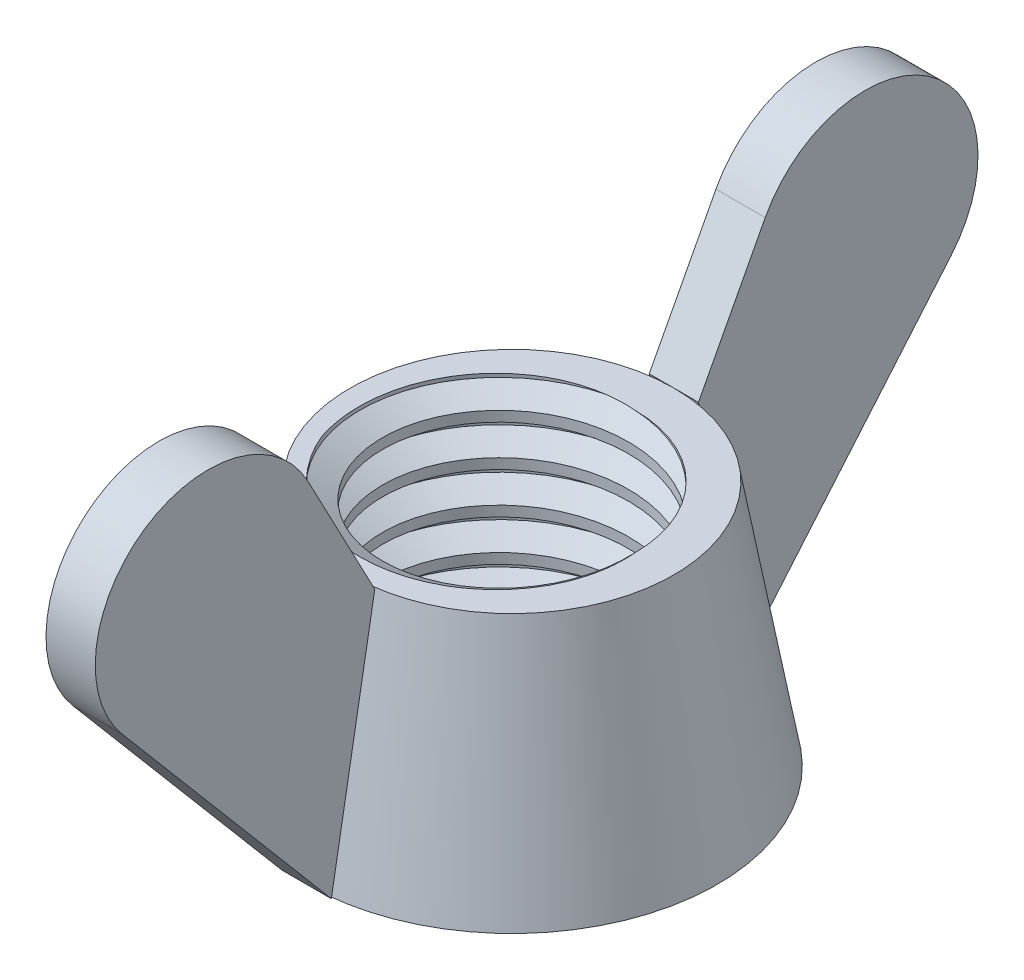
SolidWorks part; units mm, degrees
ref_plane "Front Plane" through (0, 0, 0) normal (0, 0, 1) x (1, 0, 0)
ref_plane "Top Plane" through (0, 0, 0) normal (0, 1, 0) x (1, 0, 0)
ref_plane "Right Plane" through (0, 0, 0) normal (1, 0, 0) x (0, 0, -1)
sketch "Sketch1" plane through (0, 0, 0) normal (0, 1, 0) x (1, 0, 0)
  circle A2 centre (0, 0) radius 5
  dimension "D1" = 10
extrude "Boss-Extrude1" add sketch "Sketch1" along normal blind 6 draft 10
sketch "Sketch2" plane through (0, 0, 0) normal (0, -1, 0) x (1, 0, 0)
  circle A0 centre (0, 0) radius 3
  dimension "D1" = 6
extrude "Cut-Extrude1" cut sketch "Sketch2" against normal through all
sketch "Sketch3" plane through (0, 0, 0) normal (1, 0, 0) x (0, 0, -1)
  line L0 (3.942, 6) -> (-3.942, 6) construction
  line L2 (-5, 0) -> (-10.0989, 6.0232)
  line L3 (5, 0) -> (10.0989, 6.0232)
  line L4 (-5, 0) -> (5, 0) construction
  line L5 (-3.942, 6) -> (-5.5674, 9.0826)
  line L6 (3.942, 6) -> (5.5674, 9.0826)
  line L7 (-5, 0) -> (-3.942, 6)
  line L8 (3.942, 6) -> (5, 0)
  arc A0 (-5.5674, 9.0826) -> (-10.0989, 6.0232) centre (-8, 7.8) ccw
  arc A1 (10.0989, 6.0232) -> (5.5674, 9.0826) centre (8, 7.8) ccw
  dimension "D1" = 1.8
  dimension "D2" = 8
  dimension "D3" = 16
  dimension "D4" = 5.5
extrude "Boss-Extrude2" add sketch "Sketch3" along normal mid plane 1.2 separate body
thread "Thread1" pitch 1 start angle 0, offset 1, length 6, pitch 1, diameter 6
ref_plane "Plane1" through (3, -1, 0) normal (0, 0, 1) x (1, 0, 0)
sketch "Thread Profile1" plane through (3, -1, 0) normal (0, 0, 1) x (1, 0, 0)
  line L0 (0, 0) -> (0, 1) construction
  line L1 (0, 0) -> (0.5413, 0.3125)
  line L2 (0.5413, 0.3125) -> (0.5413, 0.4375)
  line L3 (0.5413, 0.4375) -> (0, 0.75)
  line L4 (0.5413, 0.375) -> (0, 0.375) construction
  line L11 (0, 0) -> (0, 0.75)
  point P2 (0, 0)
  dimension "Pitch" = 1
  dimension "Profile_Angle" = 60
  dimension "Profile_Land" = 0.125
  dimension "Profile_Height" = 0.5413
